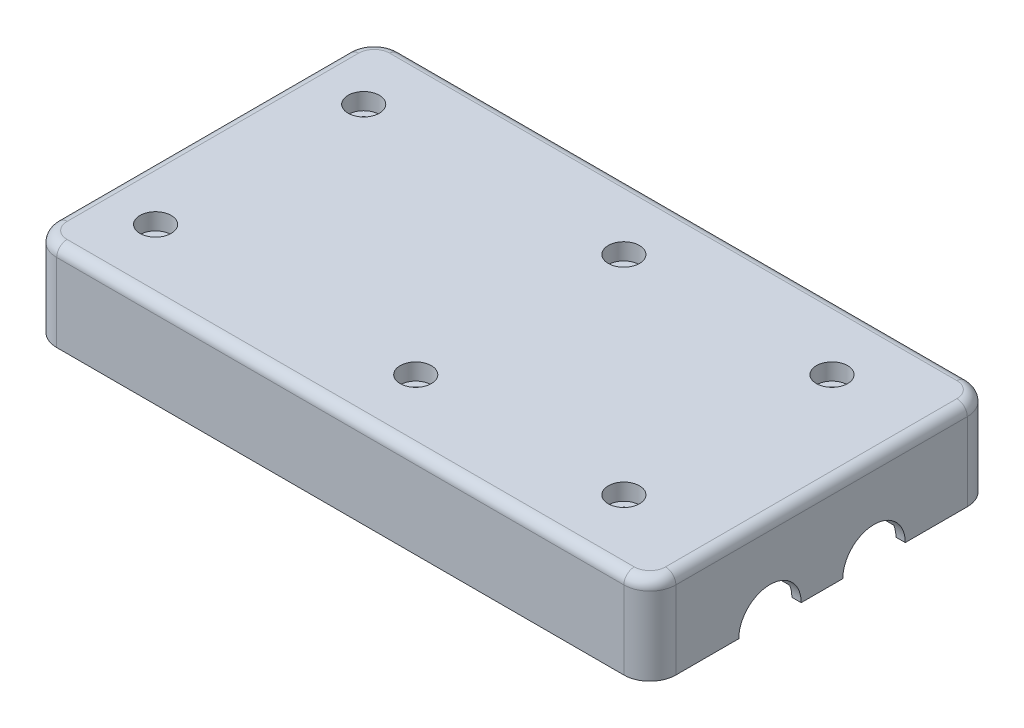
SolidWorks part; units mm, degrees
note: The reader was unsure of these and kept them because the rebuilt part matched: shared geometry of "Sketch10<3>".
ref_plane "Front Plane" through (0, 0, 0) normal (0, 0, 1) x (1, 0, 0)
ref_plane "Top Plane" through (0, 0, 0) normal (0, 1, 0) x (1, 0, 0)
ref_plane "Right Plane" through (0, 0, 0) normal (1, 0, 0) x (0, 0, -1)
sketch "Sketch1" plane through (0, 7.25, 0) normal (0, 1, 0) x (1, 0, 0)
  line L0 (-59.5, 28) -> (-59.5, 13.3004) construction
  line L1 (-54.5, -33) -> (54.5, -33)
  line L2 (-59.5, -28) -> (-59.5, 28)
  line L3 (-54.5, 33) -> (54.5, 33)
  line L4 (59.5, -28) -> (59.5, 28)
  line L5 (-59.5, -33) -> (59.5, 33) construction
  line L6 (-59.5, 33) -> (59.5, -33) construction
  line L7 (-53.5, -27) -> (53.5, -27)
  line L8 (-53.5, -27) -> (-53.5, 27)
  line L9 (-53.5, 27) -> (53.5, 27)
  line L10 (53.5, -27) -> (53.5, 27)
  line L11 (-53.5, -27) -> (53.5, 27) construction
  line L12 (-53.5, 27) -> (53.5, -27) construction
  line L13 (54.5, 33) -> (-54.5, 33) construction
  line L16 (-2.5, 27) -> (-44.5, 27) construction
  line L17 (53.5, 16.08) -> (53.5, 27) construction
  arc A0 (-54.5, -33) -> (-59.5, -28) centre (-54.5, -28) cw
  arc A1 (54.5, -33) -> (59.5, -28) centre (54.5, -28) ccw
  arc A2 (54.5, 33) -> (59.5, 28) centre (54.5, 28) cw
  arc A3 (-59.5, 28) -> (-54.5, 33) centre (-54.5, 28) cw
  point P0 (0, 0)
  point P6 (0, 0)
  dimension "D1" = 5
extrude "Boss-Extrude1" add sketch "Sketch1" along normal blind 13
sketch "Sketch2" plane through (0, 7.25, 0) normal (0, -1, 0) x (1, 0, 0)
  line L0 (-57.5, 28) -> (-57.5, -28) construction
  line L1 (-52.7, -31.2) -> (52.7, -31.2)
  line L2 (-57.7, -26.2) -> (-57.7, 26.2)
  line L3 (-52.7, 31.2) -> (52.7, 31.2)
  line L4 (57.7, -26.2) -> (57.7, 26.2)
  line L5 (-57.7, -31.2) -> (57.7, 31.2) construction
  line L6 (-57.7, 31.2) -> (57.7, -31.2) construction
  line L7 (54.5, 31) -> (-54.5, 31) construction
  arc A0 (52.7, 31.2) -> (57.7, 26.2) centre (52.7, 26.2) cw
  arc A1 (52.7, -31.2) -> (57.7, -26.2) centre (52.7, -26.2) ccw
  arc A2 (-52.7, -31.2) -> (-57.7, -26.2) centre (-52.7, -26.2) cw
  arc A3 (-57.7, 26.2) -> (-52.7, 31.2) centre (-52.7, 26.2) cw
  point P0 (0, 0)
  dimension "D3" = 5
  dimension "D1" = 0.2
  dimension "D2" = 0.2
extrude "Cut-Extrude1" cut sketch "Sketch2" against normal blind 2.2
sketch "Sketch3" plane through (0, 20.25, 0) normal (0, 1, 0) x (1, 0, 0)
  line L4 (-54.5, -33) -> (54.5, -33)
  line L5 (59.5, -28) -> (59.5, 28)
  line L6 (54.5, 33) -> (-54.5, 33)
  line L7 (-59.5, 28) -> (-59.5, -28)
  line L8 (-54.5, -33) -> (54.5, -33)
  line L9 (59.5, -28) -> (59.5, 28)
  line L10 (54.5, 33) -> (-54.5, 33)
  line L11 (-59.5, 28) -> (-59.5, -28)
  arc A4 (-59.5, -28) -> (-54.5, -33) centre (-54.5, -28) ccw
  arc A5 (54.5, -33) -> (59.5, -28) centre (54.5, -28) ccw
  arc A6 (59.5, 28) -> (54.5, 33) centre (54.5, 28) ccw
  arc A7 (-54.5, 33) -> (-59.5, 28) centre (-54.5, 28) ccw
  arc A8 (-59.5, -28) -> (-54.5, -33) centre (-54.5, -28) ccw
  arc A9 (54.5, -33) -> (59.5, -28) centre (54.5, -28) ccw
  arc A10 (59.5, 28) -> (54.5, 33) centre (54.5, 28) ccw
  arc A11 (-54.5, 33) -> (-59.5, 28) centre (-54.5, 28) ccw
  dimension "D1" = 0
extrude "Boss-Extrude2" add sketch "Sketch3" along normal blind 4
fillet "Fillet1" radius 2 8 edges at (-59.5, 24.25, 0) (-58.0355, 24.25, -31.5355) (0, 24.25, -33) (58.0355, 24.25, -31.5355) (59.5, 24.25, 0) (58.0355, 24.25, 31.5355) (0, 24.25, 33) (-58.0355, 24.25, 31.5355)
sketch "Sketch4" plane through (59.5, 0, 0) normal (1, 0, 0) x (0, 0, -1)
  circle A0 centre (-9.92, 7.2688) radius 6
  arc A1 (-15.92, 7.2688) -> (-3.92, 7.2688) centre (-9.92, 7.2688) ccw construction
  circle A2 centre (10.08, 7.2688) radius 6
  arc A3 (4.08, 7.2688) -> (16.08, 7.2688) centre (10.08, 7.2688) ccw construction
extrude "Cut-Extrude2" cut sketch "Sketch4" against normal blind 6
ref_plane "Plane1" through (-41.15, 12.1488, -17.7) normal (0, 0, -1) x (-1, 0, 0)
sketch "Sketch6" plane through (-59.5, 0, 0) normal (-1, 0, 0) x (0, 0, 1)
  line L0 (6, 11.25) -> (12, 11.25) construction
  line L1 (6, 14.25) -> (12, 14.25)
  line L2 (6, 8.25) -> (12, 8.25)
  line L3 (3, 11.25) -> (3, 7.25)
  line L4 (1.1262, 7.25) -> (28, 7.25) construction
  line L5 (15, 11.25) -> (15, 7.25)
  line L6 (-28, 7.25) -> (28, 7.25) construction
  line L7 (3, 7.25) -> (15, 7.25)
  line L8 (33, 22.25) -> (33, 7.25) construction
  circle A0 centre (-6.1, 4.4688) radius 7.2262
  arc A1 (-2.9149, -2.0176) -> (1.1262, 4.4688) centre (-6.1, 4.4688) ccw construction
  arc A2 (6, 14.25) -> (6, 8.25) centre (6, 11.25) ccw
  arc A3 (12, 8.25) -> (12, 14.25) centre (12, 11.25) ccw
  point P8 (9, 11.25)
  point P21 (6.8762, 7.25)
  point P22 (6.7811, 7.25)
  point P24 (0, 0)
  dimension "D1" = 12
  dimension "D2" = 6
  dimension "D3" = 4
  dimension "D4" = 24
extrude "Cut-Extrude3" cut sketch "Sketch6" against normal blind 6
ref_plane "Plane2" through (-36, 12.8988, 10.11) normal (-1, 0, 0) x (0, 0, 1)
sketch "Sketch9" plane through (0, 24.25, 0) normal (0, 1, 0) x (1, 0, 0)
  line L0 (-9.35, 0) -> (9.35, 0) construction
  circle A0 centre (-48.5, -20) radius 1.6
  circle A1 centre (1.5, -20) radius 1.6
  circle A2 centre (41.5, -20) radius 1.6
  circle A3 centre (41.5, 20) radius 1.6
  circle A4 centre (1.5, 20) radius 1.6
  circle A5 centre (-48.5, 20) radius 1.6
  circle A6 centre (-48.5, -20) radius 4
  circle A7 centre (1.5, -20) radius 4
  circle A8 centre (41.5, -20) radius 4
  circle A9 centre (41.5, 20) radius 4
  circle A10 centre (1.5, 20) radius 4
  circle A11 centre (-48.5, 20) radius 4
  dimension "D1" = 3.2
extrude "Boss-Extrude3" add sketch "Sketch9" against normal blind 9.75
sketch "Sketch10" plane through (0, 24.25, 0) normal (0, 1, 0) x (1, 0, 0)
  line L0 (-9.35, 0) -> (9.35, 0) construction
  circle A0 centre (-48.5, 20) radius 1.6
  circle A1 centre (1.5, 20) radius 1.6
  circle A2 centre (41.5, 20) radius 1.6
  circle A3 centre (41.5, -20) radius 1.6
  circle A4 centre (1.5, -20) radius 1.6
  circle A5 centre (-48.5, -20) radius 1.6
  circle A6 centre (-48.5, 20) radius 3
  circle A7 centre (1.5, 20) radius 3
  circle A8 centre (41.5, 20) radius 3
  circle A9 centre (41.5, -20) radius 3
  circle A10 centre (1.5, -20) radius 3
  circle A11 centre (-48.5, -20) radius 3
  dimension "D1" = 3.2
  dimension "D2" = 6
extrude "Cut-Extrude5" cut sketch "Sketch10" against normal blind 3.2 contours A6 | A11 | A7 | A10 | A9 | A8
extrude "Cut-Extrude6" cut sketch "Sketch10<3>" against normal through all contours A0 | A1 | A2 | A3 | A4 | A5
sketch "Sketch10<3>" plane through (0, 24.25, 0) normal (0, 1, 0) x (1, 0, 0) same geometry as "Sketch10"
